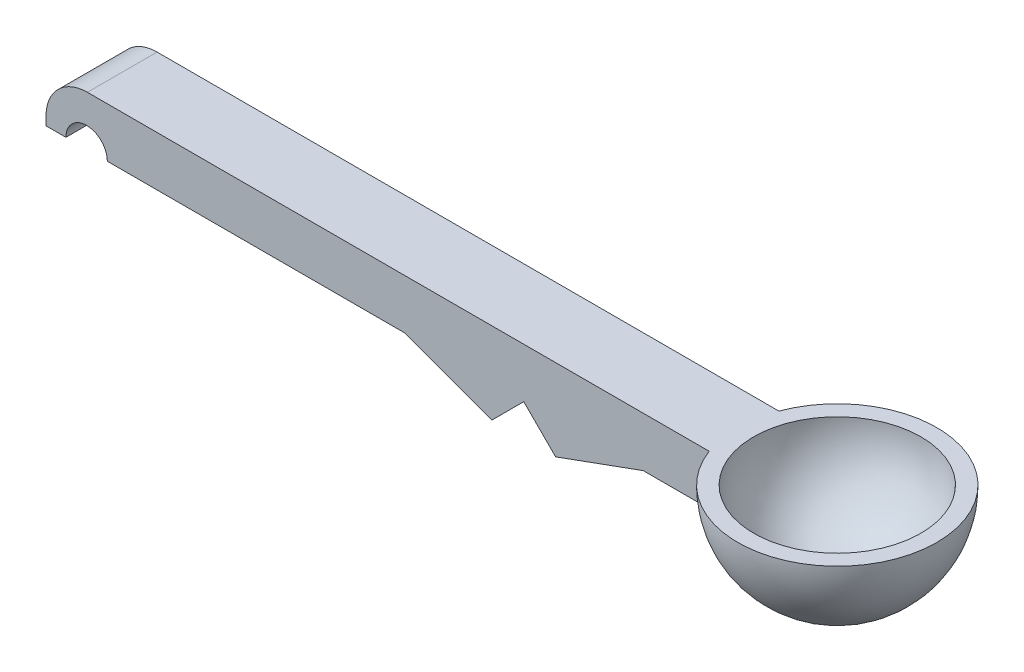
SolidWorks part; units mm, degrees
note: The reader was unsure of these and kept them because the rebuilt part matched: shared geometry of "Sketch2<4>".
ref_plane "Front Plane" through (0, 0, 0) normal (0, 0, 1) x (1, 0, 0)
ref_plane "Top Plane" through (0, 0, 0) normal (0, 1, 0) x (1, 0, 0)
ref_plane "Right Plane" through (0, 0, 0) normal (1, 0, 0) x (0, 0, -1)
sketch "Sketch1" plane through (0, 0, 0) normal (0, 1, 0) x (1, 0, 0)
  line L1 (0, 0) -> (107.95, 0)
  line L2 (0, 0) -> (0, 11.1125)
  line L3 (0, 11.1125) -> (107.95, 11.1125)
  line L4 (107.95, 0) -> (107.95, 11.1125)
  dimension "D1" = 107.95
  dimension "D2" = 11.1125
extrude "Boss-Extrude1" add sketch "Sketch1" along normal blind 7.9375
sketch "Sketch2" plane through (0, 0, 0) normal (0, 0, 1) x (1, 0, 0)
  line L0 (0, 0) -> (107.95, 0) construction
  line L1 (3.175, 0) -> (9.779, 0) construction
  line L2 (57.15, 0) -> (71.12, -5.08)
  line L3 (71.12, -5.08) -> (76.2, 0)
  line L4 (76.2, 0) -> (81.28, -5.08)
  line L5 (81.28, -5.08) -> (95.25, 0)
  line L6 (57.15, 0) -> (95.25, 0)
  line L7 (107.95, 7.9375) -> (107.95, 0) construction
  arc A0 (9.779, 0) -> (3.175, 0) centre (6.477, 0) ccw
  line M1 (0, 0) -> (107.95, 0)
  dimension "D1" = 6.604
  dimension "D2" = 3.175
  dimension "D3" = 31.75
  dimension "D4" = 12.7
  dimension "D5" = 45
  dimension "D6" = 45
  dimension "D7" = 19.05
  dimension "D8" = 5.08
extrude "Cut-Extrude1" cut sketch "Sketch2" against normal through all and the other way through all contours A0
extrude "Boss-Extrude2" add sketch "Sketch2<4>" against normal through all contours L2 L3 M1 | L4 L5 M1
sketch "Sketch2<4>" plane through (0, 0, 0) normal (0, 0, 1) x (1, 0, 0) same geometry as "Sketch2"
fillet "Fillet1" radius 6.604 1 edges at (0, 7.9375, -5.5562)
sketch "Sketch3" plane through (0, 7.9375, 0) normal (0, 1, 0) x (1, 0, 0)
  line L0 (104.775, 5.5563) -> (136.525, 5.5563) construction
  line L2 (104.775, 5.5563) -> (136.525, 5.5563)
  line L3 (107.95, 0) -> (107.95, 11.1125) construction
  arc A0 (104.775, 5.5563) -> (136.525, 5.5563) centre (120.65, 5.5563) ccw
  point P8 (107.95, 5.5563)
  dimension "D1" = 15.875
  dimension "D2" = 3.175
revolve "Revolve1" add sketch "Sketch3" angle 180 about L0
sketch "Sketch5" plane through (0, 7.9375, 0) normal (0, 1, 0) x (1, 0, 0)
  line L1 (107.315, 5.5563) -> (133.985, 5.5563)
  arc A0 (105.7791, 0) -> (105.7791, 11.1125) centre (120.65, 5.5563) ccw construction
  arc A1 (107.315, 5.5563) -> (133.985, 5.5563) centre (120.65, 5.5563) ccw
  point P9 (136.525, 5.5563)
  dimension "D1" = 26.67
  dimension "D3" = 2.54
  dimension "D2" = 2.54
revolve "Cut-Revolve2" cut sketch "Sketch5" angle 360 about L1
ref_plane "Plane1" through (0, 0, -5.5562) normal (0, 0, 1) x (1, 0, 0)
sketch "Sketch6" plane through (0, 0, -5.5562) normal (0, 0, 1) x (1, 0, 0)
  line L0 (9.779, 0) -> (57.15, 0) construction
  line L1 (16.129, 0) -> (19.304, 0)
  line L2 (16.129, 0) -> (16.129, 3.175)
  line L4 (19.304, 0) -> (19.304, 3.175)
  line L6 (19.304, 3.175) -> (19.685, 3.175)
  line L7 (16.129, 3.175) -> (16.129, 4.953)
  line L8 (16.129, 4.953) -> (19.685, 4.953)
  line L9 (19.685, 3.175) -> (19.685, 4.953)
  dimension "D1" = 3.175
  dimension "D2" = 3.556
  dimension "D3" = 1.778
  dimension "D4" = 3.175
  dimension "D5" = 6.35
revolve "Cut-Revolve3" cut sketch "Sketch6" angle 360 about L2
